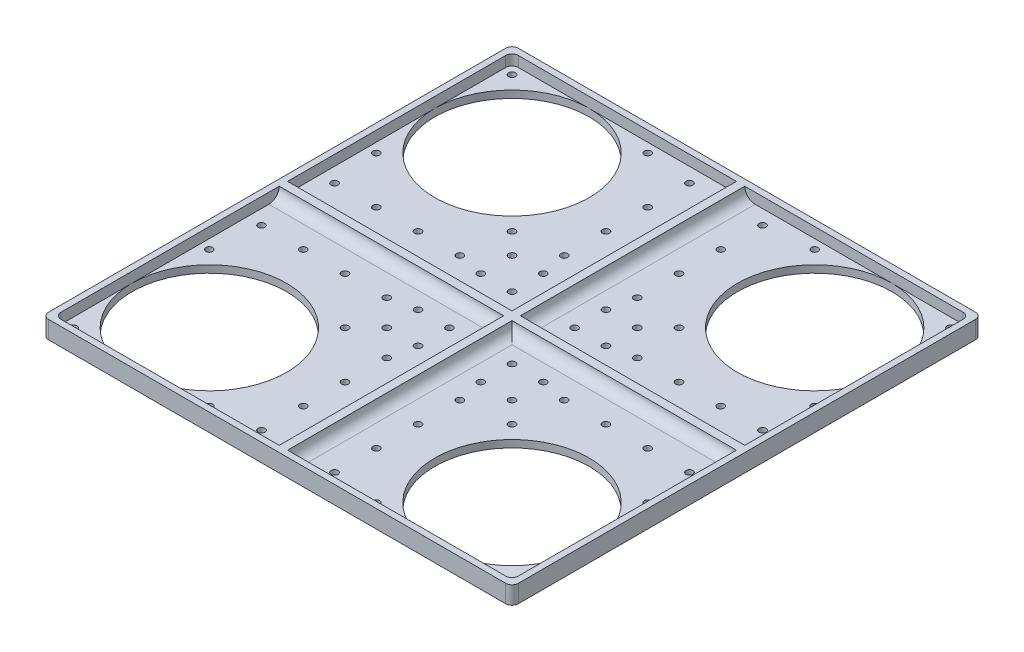
SolidWorks part; units mm, degrees
ref_plane "前视基准面" through (0, 0, 0) normal (0, 0, 1) x (1, 0, 0)
ref_plane "上视基准面" through (0, 0, 0) normal (0, 1, 0) x (1, 0, 0)
ref_plane "右视基准面" through (0, 0, 0) normal (1, 0, 0) x (0, 0, -1)
other "Configuration Table"
sketch "草图1" plane through (0, 0, 0) normal (0, 1, 0) x (1, 0, 0)
  line L1 (-112.5, -112.5) -> (112.5, -112.5)
  line L2 (-112.5, -112.5) -> (-112.5, 112.5)
  line L3 (-112.5, 112.5) -> (112.5, 112.5)
  line L4 (112.5, -112.5) -> (112.5, 112.5)
  line L5 (-112.5, -112.5) -> (112.5, 112.5) construction
  line L6 (-112.5, 112.5) -> (112.5, -112.5) construction
  point P0 (0, 0)
  dimension "D1" = 225
  dimension "D2" = 225
extrude "凸台-拉伸1" add sketch "草图1" along normal blind 3.5
sketch "草图2" plane through (0, 3.5, 0) normal (0, 1, 0) x (1, 0, 0)
  line L1 (-72.5, -72.5) -> (72.5, -72.5) construction
  line L2 (-72.5, -72.5) -> (-72.5, 72.5) construction
  line L3 (-72.5, 72.5) -> (72.5, 72.5) construction
  line L4 (72.5, -72.5) -> (72.5, 72.5) construction
  line L5 (-72.5, -72.5) -> (72.5, 72.5) construction
  line L6 (-72.5, 72.5) -> (72.5, -72.5) construction
  line L7 (112.5, 112.5) -> (-112.5, 112.5) construction
  circle A0 centre (72.5, 72.5) radius 37 construction
  circle A1 centre (-72.5, 72.5) radius 37 construction
  circle A2 centre (-72.5, -72.5) radius 37
  circle A3 centre (72.5, -72.5) radius 37 construction
  point P0 (0, 0)
  dimension "D1" = 74
  dimension "D2" = 3
extrude "切除-拉伸1" cut sketch "草图2" against normal blind 8
sketch "草图4" plane through (0, 0, 0) normal (0, -1, 0) x (1, 0, 0)
  line L1 (-105, 105) -> (-40, 105) construction
  line L2 (-105, 105) -> (-105, 40) construction
  line L3 (-105, 40) -> (-40, 40) construction
  line L4 (-40, 105) -> (-40, 40) construction
  line L5 (-105, 105) -> (-40, 40) construction
  line L6 (-105, 40) -> (-40, 105) construction
  circle A0 centre (-40, 40) radius 1.65
  circle A1 centre (-105, 40) radius 1.65
  circle A2 centre (-105, 105) radius 1.65
  circle A3 centre (-40, 105) radius 1.65
  point P0 (-72.5, 72.5)
  dimension "D2" = 3.3
  dimension "D1" = 65
extrude "切除-拉伸2" cut sketch "草图4" against normal through all
sketch "草图3" plane through (0, 3.5, 0) normal (0, 1, 0) x (1, 0, 0)
  line L0 (112.5, -112.5) -> (112.5, 112.5) construction
  line L1 (-109.5, -109.5) -> (109.5, -109.5)
  line L2 (-109.5, -109.5) -> (-109.5, 109.5)
  line L3 (-109.5, 109.5) -> (109.5, 109.5)
  line L4 (109.5, -109.5) -> (109.5, 109.5)
  line L5 (-109.5, -109.5) -> (109.5, 109.5) construction
  line L6 (-109.5, 109.5) -> (109.5, -109.5) construction
  line L7 (112.5, 112.5) -> (-112.5, 112.5) construction
  line L8 (-112.5, -112.5) -> (112.5, -112.5) construction
  line L9 (-112.5, 112.5) -> (-112.5, -112.5) construction
  line L10 (-112.5, -112.5) -> (112.5, -112.5)
  line L11 (112.5, -112.5) -> (112.5, 112.5)
  line L12 (-112.5, 112.5) -> (-112.5, -112.5)
  line L13 (112.5, 112.5) -> (-112.5, 112.5)
  line L14 (0, 112.5) -> (0, -112.5) construction
  line L15 (-112.5, 0) -> (112.5, 0) construction
  line L16 (-2, 2) -> (-2, 109.5)
  line L17 (-2, 109.5) -> (2, 109.5)
  line L18 (2, 109.5) -> (2, 2)
  line L19 (2, 2) -> (109.5, 2)
  line L20 (109.5, 2) -> (109.5, -2)
  line L21 (109.5, -2) -> (2, -2)
  line L22 (2, -2) -> (2, -109.5)
  line L23 (2, -109.5) -> (-2, -109.5)
  line L24 (-2, -109.5) -> (-2, -2)
  line L25 (-2, -2) -> (-109.5, -2)
  line L26 (-109.5, -2) -> (-109.5, 2)
  line L27 (-109.5, 2) -> (-2, 2)
  point P0 (0, 0)
  line M9 (112.5, -112.5) -> (112.5, 112.5)
  line M10 (112.5, 112.5) -> (-112.5, 112.5)
  line M11 (-112.5, 112.5) -> (-112.5, -112.5)
  line M12 (-112.5, -112.5) -> (112.5, -112.5)
  dimension "D1" = 3
  dimension "D2" = 3
  dimension "D3" = 4
extrude "加强筋" add sketch "草图3" along normal blind 5 contours L4 L1 L2 L3 M12 M9 M10 M11 | L18 L19 L20 L21 L22 L23 L24 L25 L26 L27 L16 L17 region at (-112.1818, 3.5, 0)
sketch "草图5" plane through (0, 0, 0) normal (0, -1, 0) x (1, 0, 0)
  line L0 (-112.5, 0) -> (112.5, 0) construction
  line L1 (112.5, 112.5) -> (112.5, -112.5) construction
  line L2 (-112.5, -112.5) -> (-112.5, 112.5) construction
  circle A0 centre (-102.5, 17.5) radius 1.65
  circle A1 centre (-102.5, -17.5) radius 1.65
  circle A2 centre (-82.5, 17.5) radius 1.65
  circle A3 centre (-82.5, -17.5) radius 1.65
  circle A4 centre (-62.5, 17.5) radius 1.65
  circle A5 centre (-62.5, -17.5) radius 1.65
  circle A24 centre (-42.5, 17.5) radius 1.65
  circle A25 centre (-42.5, -17.5) radius 1.65
  circle A26 centre (17.5, 42.5) radius 1.65
  circle A27 centre (-17.5, 42.5) radius 1.65
  circle A28 centre (-17.5, 62.5) radius 1.65
  circle A29 centre (17.5, 62.5) radius 1.65
  circle A30 centre (17.5, 82.5) radius 1.65
  circle A31 centre (-17.5, 82.5) radius 1.65
  circle A32 centre (-17.5, 102.5) radius 1.65
  circle A33 centre (17.5, 102.5) radius 1.65
  circle A34 centre (42.5, -17.5) radius 1.65
  circle A35 centre (42.5, 17.5) radius 1.65
  circle A36 centre (62.5, 17.5) radius 1.65
  circle A37 centre (62.5, -17.5) radius 1.65
  circle A38 centre (82.5, -17.5) radius 1.65
  circle A39 centre (82.5, 17.5) radius 1.65
  circle A40 centre (102.5, 17.5) radius 1.65
  circle A41 centre (102.5, -17.5) radius 1.65
  circle A42 centre (-17.5, -42.5) radius 1.65
  circle A43 centre (17.5, -42.5) radius 1.65
  circle A44 centre (17.5, -62.5) radius 1.65
  circle A45 centre (-17.5, -62.5) radius 1.65
  circle A46 centre (-17.5, -82.5) radius 1.65
  circle A47 centre (17.5, -82.5) radius 1.65
  circle A48 centre (17.5, -102.5) radius 1.65
  circle A49 centre (-17.5, -102.5) radius 1.65
  point P6 (0, 0)
  point P24 (-25.1023, 44.9816)
  point P25 (0, 0)
  point P60 (0, 0)
  point P76 (0, 0)
  dimension "D1" = 3.3
  dimension "D2" = 35
  dimension "D4" = 4
  dimension "D3" = 10
  dimension "D5" = 20
  dimension "D6" = 4
extrude "通用孔" cut sketch "草图5" against normal blind 10
mirror "镜向1" about plane through (0, 0, 0) normal (1, 0, 0) of "切除-拉伸1", "切除-拉伸2"
mirror "镜向2" about plane through (0, 0, 0) normal (0, 0, 1) of "镜向1"
fillet "圆角1" radius 5 8 edges at (-55.75, 3.5, -2) (55.75, 3.5, -2) (55.75, 3.5, 2) (-55.75, 3.5, 2) (-2, 3.5, 55.75) (2, 3.5, 55.75) (2, 3.5, -55.75) (-2, 3.5, -55.75)
fillet "圆角2" radius 3 8 edges at (109.5, 6, -109.5) (-109.5, 6, -109.5) (-109.5, 6, 109.5) (109.5, 6, 109.5) (112.5, 4.25, 112.5) (-112.5, 4.25, 112.5) (-112.5, 4.25, -112.5) (112.5, 4.25, -112.5)
sketch "草图6" plane through (0, 0, 0) normal (0, -1, 0) x (1, 0, 0)
  line L1 (-30, -30) -> (30, -30) construction
  line L2 (-30, -30) -> (-30, 30) construction
  line L3 (-30, 30) -> (30, 30) construction
  line L4 (30, -30) -> (30, 30) construction
  line L5 (-30, -30) -> (30, 30) construction
  line L6 (-30, 30) -> (30, -30) construction
  circle A0 centre (-30, 30) radius 1.65
  circle A1 centre (-15, 30) radius 1.65
  circle A3 centre (15, 30) radius 1.65
  circle A4 centre (30, 30) radius 1.65
  circle A5 centre (-15, 15) radius 1.65
  circle A7 centre (15, 15) radius 1.65
  circle A8 centre (30, 15) radius 1.65
  circle A13 centre (-15, -15) radius 1.65
  circle A15 centre (15, -15) radius 1.65
  circle A16 centre (30, -15) radius 1.65
  circle A17 centre (-15, -30) radius 1.65
  circle A19 centre (15, -30) radius 1.65
  circle A20 centre (30, -30) radius 1.65
  circle A21 centre (-30, 15) radius 1.65
  circle A23 centre (-30, -15) radius 1.65
  circle A24 centre (-30, -30) radius 1.65
  circle A25 centre (0, 30) radius 1.65 [skipped]
  circle A26 centre (0, 15) radius 1.65 [skipped]
  circle A27 centre (-15, 0) radius 1.65 [skipped]
  circle A28 centre (0, 0) radius 1.65 [skipped]
  circle A29 centre (15, 0) radius 1.65 [skipped]
  circle A30 centre (30, 0) radius 1.65 [skipped]
  circle A31 centre (0, -15) radius 1.65 [skipped]
  circle A32 centre (0, -30) radius 1.65 [skipped]
  circle A33 centre (-30, 0) radius 1.65 [skipped]
  point P2 (0, 0)
  dimension "D1" = 60
  dimension "D2" = 3.3
  dimension "D3" = 5
  dimension "D6" = 15
  dimension "D5" = 15
  dimension "D4" = 5
extrude "切除-拉伸3" cut sketch "草图6" against normal blind 10
